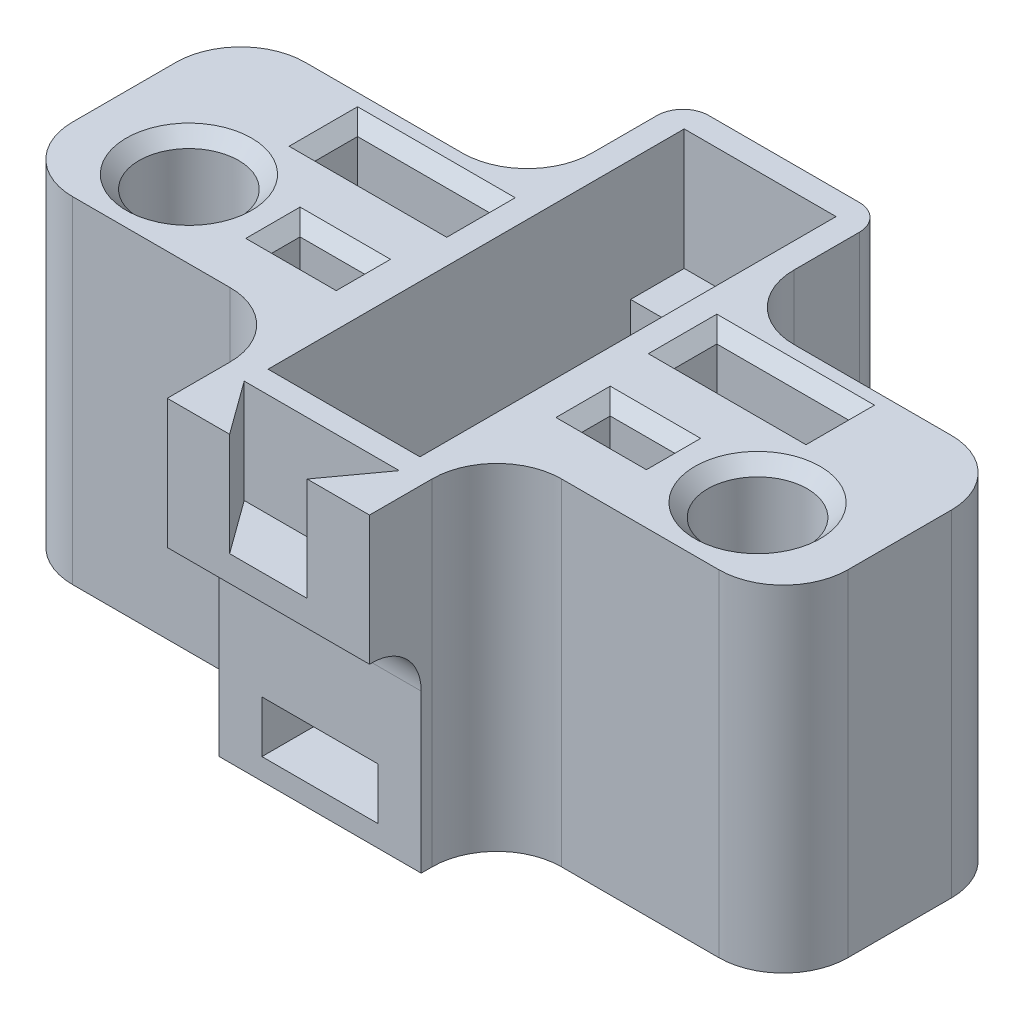
SolidWorks part; units mm, degrees
ref_plane "Front Plane" through (0, 0, 0) normal (0, 0, 1) x (1, 0, 0)
ref_plane "Top Plane" through (0, 0, 0) normal (0, 1, 0) x (1, 0, 0)
ref_plane "Right Plane" through (0, 0, 0) normal (1, 0, 0) x (0, 0, -1)
sketch "Sketch1" plane through (0, 0, 0) normal (0, 1, 0) x (1, 0, 0)
  line L1 (-30, -9) -> (30, -9)
  line L2 (-30, -9) -> (-30, 9)
  line L3 (-30, 9) -> (30, 9)
  line L4 (30, -9) -> (30, 9)
  line L5 (-30, -9) -> (30, 9) construction
  line L6 (-30, 9) -> (30, -9) construction
  point P0 (0, 0)
  dimension "D1" = 60
  dimension "D2" = 18
extrude "Boss-Extrude1" add sketch "Sketch1" along normal blind 26
sketch "Sketch2" plane through (0, 26, 0) normal (0, 1, 0) x (1, 0, 0)
  line L0 (0, 0) -> (0, -9) construction
  line L1 (-30, -9) -> (30, -9) construction
  circle A0 centre (-22, -3) radius 3.85
  circle A1 centre (22, -3) radius 3.85
  dimension "D1" = 7.7
  dimension "D2" = 7.7
  dimension "D3" = 44
  dimension "D4" = 22
  dimension "D5" = 6
  dimension "D6" = 6
extrude "Eyeshaft holes" cut sketch "Sketch2" against normal blind 15
fillet "Eyeshaft Fillet" radius 3 2 edges at (22, 11, 6.85) (-22, 11, 6.85)
sketch "Sketch5" plane through (0, 26, 0) normal (0, 1, 0) x (1, 0, 0)
  line L0 (-22, -3) -> (22, -3) construction
  line L2 (-14.5, -4.1) -> (-9.5, -4.1)
  line L3 (-14.5, -4.1) -> (-14.5, -1.9)
  line L4 (-14.5, -1.9) -> (-9.5, -1.9)
  line L5 (-9.5, -4.1) -> (-9.5, -1.9)
  line L6 (-14.5, -4.1) -> (-9.5, -1.9) construction
  line L7 (-14.5, -1.9) -> (-9.5, -4.1) construction
  line L8 (9.5, -4.1) -> (14.5, -4.1)
  line L9 (9.5, -4.1) -> (9.5, -1.9)
  line L10 (9.5, -1.9) -> (14.5, -1.9)
  line L11 (14.5, -4.1) -> (14.5, -1.9)
  line L12 (9.5, -4.1) -> (14.5, -1.9) construction
  line L13 (9.5, -1.9) -> (14.5, -4.1) construction
  point P4 (-12, -3)
  point P9 (12, -3)
  dimension "D1" = 2.2
  dimension "D2" = 5
  dimension "D3" = 5
  dimension "D4" = 2.2
  dimension "D5" = 10
  dimension "D6" = 10
extrude "Front leg holes" cut sketch "Sketch5" against normal blind 13
sketch "Sketch7" plane through (0, 26, 0) normal (0, 1, 0) x (1, 0, 0)
  line L1 (-19, 7.05) -> (-8.8, 7.05)
  line L2 (-19, 7.05) -> (-19, 3.75)
  line L3 (-19, 3.75) -> (-8.8, 3.75)
  line L4 (-8.8, 7.05) -> (-8.8, 3.75)
  line L5 (8.8, 7.05) -> (19, 7.05)
  line L6 (8.8, 7.05) -> (8.8, 3.75)
  line L7 (8.8, 3.75) -> (19, 3.75)
  line L8 (19, 7.05) -> (19, 3.75)
  circle A0 centre (-22, -3) radius 3.85 construction
  circle A2 centre (22, -3) radius 3.85 construction
  point P16 (-20.2379, 3.75)
  dimension "D1" = 3.3
  dimension "D2" = 10.2
  dimension "D3" = 10.2
  dimension "D4" = 3.3
  dimension "D5" = 10.05
  dimension "D6" = 10.05
  dimension "D7" = 3
  dimension "D8" = 3
extrude "Back Legs" cut sketch "Sketch7" against normal blind 13
sketch "Sketch18" plane through (0, 26, 0) normal (0, 1, 0) x (1, 0, 0)
  line L0 (0, 9) -> (0, -9) construction
  line L1 (30, 9) -> (-30, 9) construction
  line L2 (-30, -9) -> (30, -9) construction
  line L3 (-22, -3) -> (22, -3) construction
  line L4 (-7.825, -14.85) -> (7.825, -14.85)
  line L5 (-7.825, -14.85) -> (-7.825, 21.05)
  line L6 (-7.825, 21.05) -> (7.825, 21.05)
  line L7 (7.825, -14.85) -> (7.825, 21.05)
  line L8 (-7.825, -14.85) -> (7.825, 21.05) construction
  line L9 (-7.825, 21.05) -> (7.825, -14.85) construction
  point P6 (0, 3.1)
  dimension "D1" = 24.05
  dimension "D2" = 11.85
  dimension "D3" = 15.65
extrude "Servo Block" add sketch "Sketch18" against normal up to surface (26 mm away) up to face at (0, 0, 0)
sketch "Sketch19" plane through (0, 26, 0) normal (0, 1, 0) x (1, 0, 0)
  line L0 (0, 21.05) -> (0, -14.85) construction
  line L1 (7.825, 21.05) -> (-7.825, 21.05) construction
  line L2 (-7.825, -14.85) -> (7.825, -14.85) construction
  line L3 (-22, -3) -> (22, -3) construction
  line L5 (-5.875, -13) -> (5.875, -13)
  line L6 (-5.875, -13) -> (-5.875, 19.2)
  line L7 (-5.875, 19.2) -> (5.875, 19.2)
  line L8 (5.875, -13) -> (5.875, 19.2)
  line L9 (-5.875, -13) -> (5.875, 19.2) construction
  line L10 (-5.875, 19.2) -> (5.875, -13) construction
  point P10 (0, 3.1)
  dimension "D1" = 22.2
  dimension "D2" = 10
  dimension "D3" = 11.75
extrude "Servo Arms" cut sketch "Sketch19" against normal blind 9.35
sketch "Sketch20" plane through (0, 16.65, 0) normal (0, 1, 0) x (1, 0, 0)
  line L0 (-22, -3) -> (22, -3) construction
  line L1 (0, -13) -> (0, 19.2) construction
  line L2 (-5.875, -13) -> (5.875, -13) construction
  line L3 (5.875, 19.2) -> (-5.875, 19.2) construction
  line L5 (-5.875, 15.05) -> (5.875, 15.05)
  line L6 (-5.875, 15.05) -> (-5.875, -8.85)
  line L7 (-5.875, -8.85) -> (5.875, -8.85)
  line L8 (5.875, 15.05) -> (5.875, -8.85)
  line L9 (-5.875, 15.05) -> (5.875, -8.85) construction
  line L10 (-5.875, -8.85) -> (5.875, 15.05) construction
  point P10 (0, 3.1)
  dimension "D1" = 5.85
  dimension "D2" = 18.05
  dimension "D3" = 11.75
extrude "Cut-Extrude10" cut sketch "Sketch20" against normal blind 15
sketch "Sketch15" [suppressed] plane through (0, 0, 17.5) normal (0, 0, 1) x (1, 0, 0)
  line L0 (0, 0) -> (0, 26) construction
  line L1 (-10, 0) -> (10, 0) construction
  line L2 (10, 26) -> (-10, 26) construction
  line L4 (-4.5, 1.4) -> (4.5, 1.4)
  line L5 (-4.5, 1.4) -> (-4.5, 5.4)
  line L6 (-4.5, 5.4) -> (4.5, 5.4)
  line L7 (4.5, 1.4) -> (4.5, 5.4)
  line L8 (-4.5, 1.4) -> (4.5, 5.4) construction
  line L9 (-4.5, 5.4) -> (4.5, 1.4) construction
  point P6 (0, 3.4)
  dimension "D1" = 9
  dimension "D2" = 4
  dimension "D3" = 1.4
sketch "Sketch16" [suppressed] plane through (0, 12.4, 0) normal (0, 1, 0) x (1, 0, 0)
  line L0 (-6.1, -12) -> (6.1, -12) construction
  line L1 (-2.5, -12.5) -> (2.5, -12.5)
  line L2 (-2.5, -12.5) -> (-2.5, -11.5)
  line L3 (-2.5, -11.5) -> (2.5, -11.5)
  line L4 (2.5, -12.5) -> (2.5, -11.5)
  line L5 (-2.5, -12.5) -> (2.5, -11.5) construction
  line L6 (-2.5, -11.5) -> (2.5, -12.5) construction
  point P0 (0, -12)
  dimension "D1" = 5
  dimension "D2" = 1
sketch "Sketch13" [suppressed] plane through (0, 12.4, 0) normal (0, 1, 0) x (1, 0, 0)
  line L1 (6.1, 13) -> (6.1, 16.6) construction
  line L2 (6.1, 13) -> (-6.1, 13) construction
  line L4 (6.1, -16.6) -> (6.1, -12) construction
  line L5 (-2.5, -12.5) -> (2.5, -12.5) construction
  circle A0 centre (0.1, 15) radius 0.5
  circle A1 centre (0.1, -14.5) radius 0.5
  dimension "D2" = 6
  dimension "D3" = 1
  dimension "D4" = 1
  dimension "D1" = 2
  dimension "D5" = 2
  dimension "D6" = 6
fillet "Fillet3" [suppressed] radius 2
sketch "Sketch17" plane through (0, 26, 0) normal (0, 1, 0) x (1, 0, 0)
  line L1 (-5.9, -16.2) -> (5.9, -16.2)
  line L2 (-5.9, -16.2) -> (-5.9, 16.2)
  line L3 (-5.9, 16.2) -> (5.9, 16.2)
  line L4 (5.9, -16.2) -> (5.9, 16.2)
  line L5 (-5.9, -16.2) -> (5.9, 16.2) construction
  line L6 (-5.9, 16.2) -> (5.9, -16.2) construction
  point P0 (0, 0)
  dimension "D1" = 11.8
  dimension "D2" = 32.4
extrude "Servo Body" [suppressed] cut sketch "Sketch17" against normal blind 24
ref_axis "Axis1" through (-22, 14, 3) along (0, 1, 0)
ref_axis "Axis2" through (22, 14, 3) along (0, 1, 0)
ref_plane "Plane2" through (0, 0, 3) normal (0, 0, 1) x (1, 0, 0)
fillet "Fillet4" radius 5 4 edges at (30, 13, -9) (30, 13, 9) (-30, 13, 9) (-30, 13, -9)
chamfer "Chamfer1" distance 1 angle 45 18 edges at (22, 26, 6.85) (-22, 26, 6.85) (-14.5, 26, 3) (-12, 26, 4.1) (-12, 26, 1.9) (-9.5, 26, 3) (14.5, 26, 3) (12, 26, 4.1) (9.5, 26, 3) (12, 26, 1.9) (19, 26, -5.4) (13.9, 26, -3.75) (8.8, 26, -5.4) (13.9, 26, -7.05) (-8.8, 26, -5.4) (-13.9, 26, -3.75) (-19, 26, -5.4) (-13.9, 26, -7.05)
sketch "Sketch21" plane through (0, 0, 8.85) normal (0, 0, -1) x (-1, 0, 0)
  line L0 (0, 1.65) -> (0, 16.65) construction
  line L1 (5.875, 1.65) -> (-5.875, 1.65) construction
  line L2 (5.875, 16.65) -> (-5.875, 16.65) construction
  line L3 (4.5, 5.65) -> (-4.5, 5.65)
  line L4 (4.5, 5.65) -> (4.5, 1.65)
  line L5 (-4.5, 5.65) -> (-4.5, 1.65)
  line L6 (4.5, 1.65) -> (-4.5, 1.65)
  line L7 (4.5, 5.65) -> (-4.5, 1.65) construction
  line L8 (-4.5, 5.65) -> (4.5, 1.65) construction
  point P7 (0, 3.65)
  dimension "D1" = 9
  dimension "D2" = 0
  dimension "D3" = 4
  dimension "D4" = 0
extrude "Cut-Extrude11" cut sketch "Sketch21" against normal blind 15
fillet "Fillet5" radius 3 1 edges at (0, 5.65, 8.85)
sketch "Sketch22" plane through (0, 16.65, 0) normal (0, 1, 0) x (1, 0, 0)
  line L0 (5.875, 15.05) -> (-5.875, 15.05) construction
  line L1 (-5.875, -8.85) -> (5.875, -8.85) construction
  circle A0 centre (0, 17.3) radius 0.75
  circle A1 centre (0, -11.1) radius 0.75
  dimension "D1" = 2.25
  dimension "D2" = 1.5
  dimension "D3" = 1.5
  dimension "D4" = 2.25
extrude "Cut-Extrude12" cut sketch "Sketch22" against normal blind 3
fillet "Fillet6" radius 5 4 edges at (-7.825, 13, 9) (7.825, 13, 9) (7.825, 13, -9) (-7.825, 13, -9)
sketch "Sketch23" plane through (0, 0, 14.85) normal (0, 0, 1) x (1, 0, 0)
  line L0 (0, 26) -> (0, 5.65) construction
  line L1 (-7.825, 26) -> (7.825, 26) construction
  line L2 (4.5, 5.65) -> (-4.5, 5.65) construction
  line L4 (-7.825, 16) -> (7.825, 16)
  line L5 (-7.825, 16) -> (-7.825, 26)
  line L6 (-7.825, 26) -> (7.825, 26)
  line L7 (7.825, 16) -> (7.825, 26)
  line L8 (-7.825, 16) -> (7.825, 26) construction
  line L9 (-7.825, 26) -> (7.825, 16) construction
  point P6 (0, 21)
  dimension "D1" = 10
extrude "Boss-Extrude3" add sketch "Sketch23" along normal blind 4
sketch "Sketch24" plane through (0, 26, 0) normal (0, 1, 0) x (1, 0, 0)
  line L0 (7.825, -18.85) -> (-7.825, -18.85) construction
  line L1 (-5.9986, -22.9772) -> (5.9986, -22.9772)
  line L2 (-5.9986, -22.9772) -> (-5.9986, -14.7228)
  line L3 (-5.9986, -14.7228) -> (5.9986, -14.7228)
  line L4 (5.9986, -22.9772) -> (5.9986, -14.7228)
  line L5 (-5.9986, -22.9772) -> (5.9986, -14.7228) construction
  line L6 (-5.9986, -14.7228) -> (5.9986, -22.9772) construction
  line L7 (-5.9986, -14.7228) -> (-3, -18.85)
  line L8 (-3, -18.85) -> (3, -18.85)
  line L9 (3, -18.85) -> (5.9986, -14.7228)
  point P0 (0, -18.85)
  line M41 (-7.825, -18.85) -> (7.825, -18.85)
  dimension "D1" = 6
  dimension "D2" = 126
  dimension "D3" = 126
extrude "Cut-Extrude13" cut sketch "Sketch24" against normal blind 8 contours L9 L3 L7 M41 region at (0, 26, 16.5572)
fillet "Fillet7" [suppressed] radius 1
fillet "Fillet8" radius 3.8 1 edges at (0, 16, 14.85)
fillet "Fillet9" radius 2 2 edges at (7.825, 13, -21.05) (-7.825, 13, -21.05)
